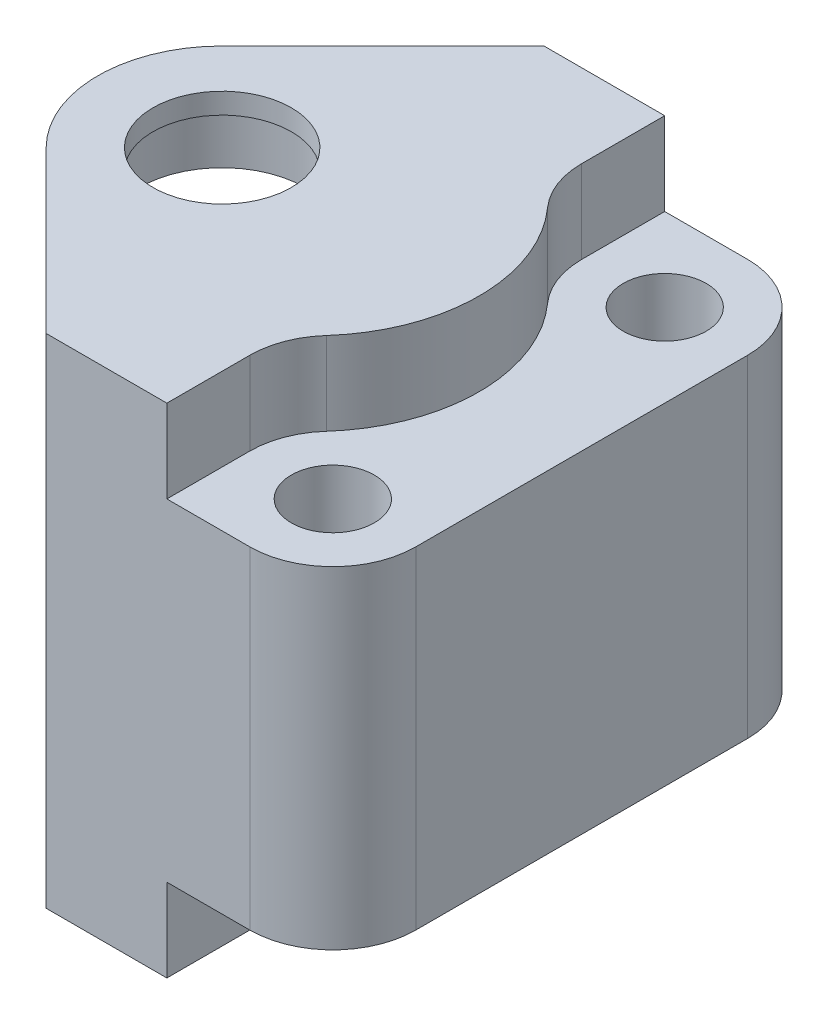
SolidWorks part; units mm, degrees
ref_plane "Front Plane" through (0, 0, 0) normal (0, 0, 1) x (1, 0, 0)
ref_plane "Top Plane" through (0, 0, 0) normal (0, 1, 0) x (1, 0, 0)
ref_plane "Right Plane" through (0, 0, 0) normal (1, 0, 0) x (0, 0, -1)
sketch "Sketch1" plane through (0, 0, 0) normal (0, 1, 0) x (1, 0, 0)
  line L1 (13, 6) -> (13, -6)
  line L2 (-8.0641, 0) -> (21.3803, 0) construction
  line L4 (-3.182, 3.182) -> (2.636, 9)
  line L5 (2.636, 9) -> (10, 9)
  line L6 (-3.182, -3.182) -> (2.636, -9)
  line L7 (2.636, -9) -> (10, -9)
  circle A1 centre (0, 0) radius 3 construction
  circle A2 centre (10, 6) radius 1.5
  circle A3 centre (10, -6) radius 1.5
  arc A4 (-3.182, -3.182) -> (-3.182, 3.182) centre (0, 0) cw
  arc A5 (10, 9) -> (13, 6) centre (10, 6) cw
  arc A6 (10, -9) -> (13, -6) centre (10, -6) ccw
  point P1 (0, 0)
  point P16 (13, 0)
  dimension "D1" = 12
  dimension "D2" = 6
  dimension "D3" = 3
  dimension "D4" = 4.5
  dimension "D5" = 3
  dimension "D6" = 10
  dimension "D7" = 18
  dimension "D8" = 90
extrude "Boss-Extrude1" add sketch "Sketch1" along normal mid plane 18
sketch "Sketch2" plane through (0, 0, 0) normal (0, 1, 0) x (1, 0, 0)
  line L0 (5.001, 1.5977) -> (2.636, 9)
  line L5 (2.636, -9) -> (5.001, -1.5977)
  line L6 (-3.182, -3.182) -> (2.636, -9) construction
  line L7 (2.636, 9) -> (-3.182, 3.182) construction
  line L8 (-3.182, -3.182) -> (2.636, -9)
  line L9 (2.636, 9) -> (-3.182, 3.182)
  arc A0 (5.001, 1.5977) -> (5.001, -1.5977) centre (0, 0) cw
  arc A2 (-3.182, 3.182) -> (-3.182, -3.182) centre (0, 0) ccw construction
  arc A3 (-3.182, 3.182) -> (-3.182, -3.182) centre (0, 0) ccw
  point P0 (2.636, -9)
  dimension "D2" = 5.25
extrude "Cut-Extrude1" cut sketch "Sketch2" along normal mid plane 12.5
sketch "Sketch3" plane through (0, 0, 0) normal (0, 0, 1) x (1, 0, 0)
  line L0 (0, -11.5038) -> (0, 11.5038) construction
  line L1 (-2.5, 9) -> (-2.5, 8.25)
  line L3 (-2.5, 8.25) -> (-3, 8.25)
  line L4 (-3, 8.25) -> (-3, 6.25)
  line L6 (-3, 6.25) -> (0, 6.25)
  line L7 (0, 6.25) -> (0, 9)
  line L8 (0, 9) -> (-2.5, 9)
  line L9 (6.0691, 0) -> (-6.0691, 0) construction
  line L10 (0, -6.25) -> (0, -9)
  line L11 (0, -9) -> (-2.5, -9)
  line L12 (-3, -6.25) -> (0, -6.25)
  line L13 (-3, -8.25) -> (-3, -6.25)
  line L14 (-2.5, -8.25) -> (-3, -8.25)
  line L15 (-2.5, -9) -> (-2.5, -8.25)
  line L16 (-3.182, 9) -> (2.636, 9) construction
  line L17 (-3.182, 6.25) -> (2.636, 6.25) construction
  point P4 (0, 0)
  point P7 (-2.5, 9)
  point P13 (-3, 6.25)
  point P18 (0, 0)
  point P24 (0, 0)
  point P25 (0, 0)
  point P26 (0, 0)
  dimension "D1" = 2
  dimension "D2" = 0.5
  dimension "D3" = 6
revolve "Cut-Revolve1" cut sketch "Sketch3" angle 360 about L0
sketch "Sketch4" plane through (0, 0, 0) normal (0, 1, 0) x (1, 0, 0)
  line L0 (0, 0) -> (14.4535, 0) construction
  line L1 (2.636, -9) -> (10, -9) construction
  line L2 (13, -6) -> (13, 6) construction
  line L3 (10, 9) -> (2.636, 9) construction
  line L4 (7, -9) -> (10, -9)
  line L5 (13, -6) -> (13, 6)
  line L6 (10, 9) -> (7, 9)
  line L7 (7, 6) -> (7, 9)
  line L8 (7, -6) -> (7, -9)
  arc A0 (7, 6) -> (7.7639, 4) centre (10, 6) ccw
  arc A1 (7.7639, 4) -> (7.7639, -4) centre (3.2918, 0) cw
  arc A2 (7.7639, -4) -> (7, -6) centre (10, -6) ccw
  arc A3 (10, -9) -> (13, -6) centre (10, -6) ccw construction
  arc A4 (13, 6) -> (10, 9) centre (10, 6) ccw construction
  arc A5 (10, -9) -> (13, -6) centre (10, -6) ccw
  arc A6 (13, 6) -> (10, 9) centre (10, 6) ccw
  dimension "D1" = 3
  dimension "D2" = 6
extrude "Cut-Extrude2" cut sketch "Sketch4" against normal blind 3 from surface starting at face at (0, 9, -2.5)
extrude "Cut-Extrude3" cut sketch "Sketch4<2>" along normal blind 3 from surface starting at face at (0, -9, -2.5)
sketch "Sketch4<2>" plane through (0, 0, 0) normal (0, 1, 0) x (1, 0, 0) same geometry as "Sketch4"
